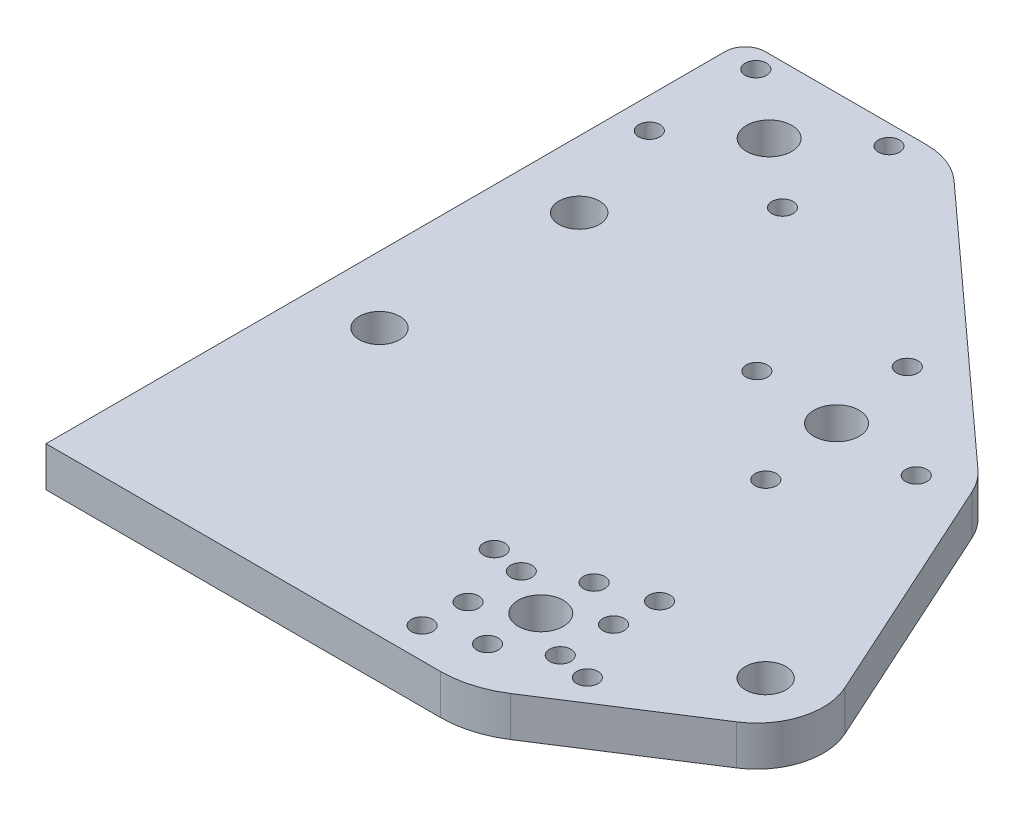
SolidWorks part; units mm, degrees
ref_plane "Plano frontal" through (0, 0, 0) normal (0, 0, 1) x (1, 0, 0)
ref_plane "Plano superior" through (0, 0, 0) normal (0, 1, 0) x (1, 0, 0)
ref_plane "Plano direito" through (0, 0, 0) normal (1, 0, 0) x (0, 0, -1)
ref_plane "Plano1" through (0, -6, 0) normal (0, -1, 0) x (1, 0, 0)
sketch "Esboço1" plane through (0, -6, 0) normal (0, -1, 0) x (1, 0, 0)
  line L0 (151.2357, -14.2909) -> (167.1948, 20.7865)
  line L1 (163.5005, 33.3393) -> (142.8288, 46.6294)
  line L2 (134.6661, 49.0269) -> (75.4374, 49.0269)
  line L3 (75.4374, 49.0269) -> (75.4374, -53)
  line L4 (78.4374, -56) -> (102.6847, -56)
  line L5 (109.4101, -53.4005) -> (148.859, -17.5502)
  line L6 (134.1775, -0.3541) -> (144.9383, -12.195) construction
  line L7 (144.9383, -12.195) -> (130.1372, -25.6459) construction
  line L8 (130.1372, -25.6459) -> (119.3765, -13.805) construction
  line L9 (119.3765, -13.805) -> (134.1775, -0.3541) construction
  line L10 (134.1775, -0.3541) -> (130.1372, -25.6459) construction
  line L11 (100.0374, -37) -> (80.0374, -53) construction
  line L12 (127.326, 44.4269) -> (146.5154, 38.7906) construction
  line L13 (146.5154, 38.7906) -> (142.0063, 23.4391) construction
  line L14 (142.0063, 23.4391) -> (122.8169, 29.0754) construction
  line L15 (122.8169, 29.0754) -> (127.326, 44.4269) construction
  line L16 (127.326, 44.4269) -> (142.0063, 23.4391) construction
  line L17 (134.6661, 33.933) -> (138.9199, 48.4151) construction
  circle A0 centre (119.3765, -13.805) radius 1.6
  circle A1 centre (146.5154, 38.7906) radius 1.6
  circle A2 centre (142.0063, 23.4391) radius 1.6
  circle A3 centre (159.9953, 25.4877) radius 3.05
  circle A4 centre (100.0374, -37) radius 1.6
  circle A5 centre (100.0374, -53) radius 1.6
  circle A6 centre (80.0374, -37) radius 1.6
  circle A7 centre (80.0374, -53) radius 1.6
  circle A8 centre (122.8169, 29.0754) radius 1.6
  circle A9 centre (127.326, 44.4269) radius 1.6
  circle A10 centre (130.1372, -25.6459) radius 1.6
  circle A11 centre (144.9383, -12.195) radius 1.6
  circle A12 centre (134.1775, -0.3541) radius 1.6
  circle A13 centre (141.5943, 29.933) radius 1.6
  circle A14 centre (134.6661, 25.933) radius 1.6
  circle A15 centre (127.7379, 29.933) radius 1.6
  circle A16 centre (127.7379, 37.933) radius 1.6
  circle A17 centre (134.6661, 41.933) radius 1.6
  circle A18 centre (141.5943, 37.933) radius 1.6
  circle A19 centre (134.6661, 33.933) radius 3.4
  circle A20 centre (132.1574, -13) radius 3.4
  circle A21 centre (90.0374, -45) radius 3.4
  arc A22 (167.1948, 20.7865) -> (163.5005, 33.3393) centre (158.0926, 24.9277) ccw
  arc A23 (142.8288, 46.6294) -> (134.6661, 49.0269) centre (134.6661, 33.933) ccw
  arc A24 (75.4374, -53) -> (78.4374, -56) centre (78.4374, -53) ccw
  arc A25 (102.6847, -56) -> (109.4101, -53.4005) centre (102.6847, -46) ccw
  arc A26 (148.859, -17.5502) -> (151.2357, -14.2909) centre (142.1335, -10.1497) ccw
  point P27 (129.2621, 29.5969)
  point P28 (0, 0)
  point P62 (134.6661, 33.933)
  point P63 (0, 0)
  point P64 (141.5943, 37.933)
  dimension "D4" = 10
  dimension "D5" = 6.1
  dimension "D8" = 6.8
  dimension "D9" = 3.2
  dimension "D24" = 3
  dimension "D1" = 105.0269
  dimension "D2" = 11
  dimension "D3" = 82.6552
  dimension "D6" = 80.9277
  dimension "D7" = 137.736
  dimension "D10" = 20
  dimension "D11" = 16
  dimension "D12" = 6.6
  dimension "D13" = 52.897
  dimension "D14" = 43
  dimension "D15" = 16
  dimension "D16" = 46.933
  dimension "D17" = 59.2287
  dimension "D18" = 14.6
  dimension "D19" = 8
  dimension "D21" = 26.7
  dimension "D22" = 47.5
  dimension "D23" = 6.6
  dimension "D20" = 6
extrude "Ressalto-extrusão1" add sketch "Esboço1" against normal blind 6
sketch "Esboço2" plane through (0, -6, 0) normal (0, -1, 0) x (1, 0, 0)
  line L0 (75.4374, 49.0269) -> (75.4374, -53) construction
  line L1 (78.428, 16.433) -> (146.9239, 16.433) construction
  circle A0 centre (85.4374, 8.933) radius 3.05
  circle A1 centre (85.4374, -21.067) radius 3.05
  circle A2 centre (85.4374, 8.933) radius 7.5 construction
  circle A3 centre (85.4374, -21.067) radius 7.5 construction
  circle A4 centre (134.6661, 33.933) radius 3.4 construction
  point P6 (127.9122, 23.3655)
  point P13 (146.7891, 21.8391)
  dimension "D1" = 6.1
  dimension "D2" = 15
  dimension "D3" = 30
  dimension "D5" = 25
  dimension "D4" = 10
extrude "Corte-extrusão1" cut sketch "Esboço2" against normal blind 10 contours A1 | A0 region at (85.4374, -6, -21.067)
